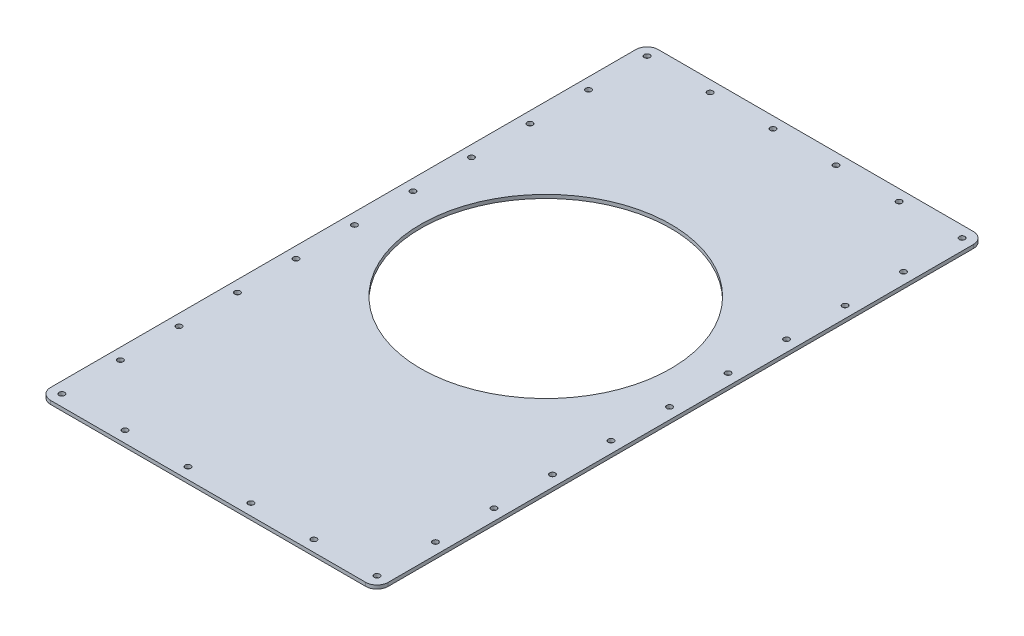
SolidWorks part; units mm, degrees
material "5052-H32"
ref_plane "Front Plane" through (0, 0, 0) normal (0, 0, 1) x (1, 0, 0)
ref_plane "Top Plane" through (0, 0, 0) normal (0, 1, 0) x (1, 0, 0)
ref_plane "Right Plane" through (0, 0, 0) normal (1, 0, 0) x (0, 0, -1)
sketch "Sketch9" plane through (0, 0, 0) normal (0, 1, 0) x (1, 0, 0)
  line L1 (-125, 500) -> (135, 500) construction
  line L2 (-125, 500) -> (-125, 0) construction
  line L3 (-125, 0) -> (135, 0) construction
  line L4 (135, 500) -> (135, 0) construction
  line L8 (-145, 520) -> (-145, -20)
  line L9 (-145, -20) -> (155, -20)
  line L10 (155, 520) -> (155, -20)
  line L11 (-145, 520) -> (155, 520)
  circle A0 centre (-135, -10) radius 2.5
  circle A2 centre (-135, 42) radius 2.5
  circle A3 centre (-135, 94) radius 2.5
  circle A4 centre (-135, 146) radius 2.5
  circle A5 centre (-135, 198) radius 2.5
  circle A6 centre (-135, 250) radius 2.5
  circle A7 centre (-135, 302) radius 2.5
  circle A8 centre (-135, 354) radius 2.5
  circle A9 centre (-135, 406) radius 2.5
  circle A10 centre (-135, 458) radius 2.5
  circle A16 centre (-135, 510) radius 2.5
  circle A17 centre (-79, 510) radius 2.5
  circle A18 centre (-23, 510) radius 2.5
  circle A19 centre (33, 510) radius 2.5
  circle A20 centre (89, 510) radius 2.5
  circle A21 centre (145, 510) radius 2.5
  circle A22 centre (145, 458) radius 2.5
  circle A23 centre (145, 406) radius 2.5
  circle A24 centre (145, 354) radius 2.5
  circle A25 centre (145, 302) radius 2.5
  circle A26 centre (145, 250) radius 2.5
  circle A27 centre (145, 198) radius 2.5
  circle A28 centre (145, 146) radius 2.5
  circle A29 centre (145, 94) radius 2.5
  circle A30 centre (145, 42) radius 2.5
  circle A31 centre (145, -10) radius 2.5
  circle A37 centre (5, 280) radius 111.125
  circle A38 centre (89, -10) radius 2.5
  circle A39 centre (33, -10) radius 2.5
  circle A40 centre (-23, -10) radius 2.5
  circle A41 centre (-79, -10) radius 2.5
  dimension "D4" = 5
  dimension "D13" = 222.25
  dimension "D2" = 10
  dimension "D3" = 10
  dimension "D10" = 500
  dimension "D12" = 220
  dimension "D9" = 260
  dimension "D11" = 130
  dimension "D1" = 20
  dimension "D8" = 11
  dimension "D5" = 6
  dimension "D6" = 11
  dimension "D7" = 5
extrude "Boss-Extrude7" add sketch "Sketch9" along normal blind 3.175 separate body contours L11 L8 L9 L10 A37 A41 A31 A30 A29 A28 A27 A26 A25 A24 A23 A22 A21 A20 A19 A18 A17 A16 A10 | A37 region at (5, 0, -513.8226) region at (5, 0, -280)
fillet "Fillet4" radius 10 4 edges at (-145, 1.5875, -520) (155, 1.5875, -520) (155, 1.5875, 20) (-145, 1.5875, 20)
extrude "Cut-Extrude1" cut sketch "Sketch9<3>" along normal through all both and the other way through all contours A37
sketch "Sketch9<3>" plane through (0, 0, 0) normal (0, 1, 0) x (1, 0, 0) same geometry as "Sketch9"
equation "\"W\"= 260"
equation "\"D9@Sketch9\"=\"W\""
equation "\"D11@Sketch9\"=\"W\"/2"
